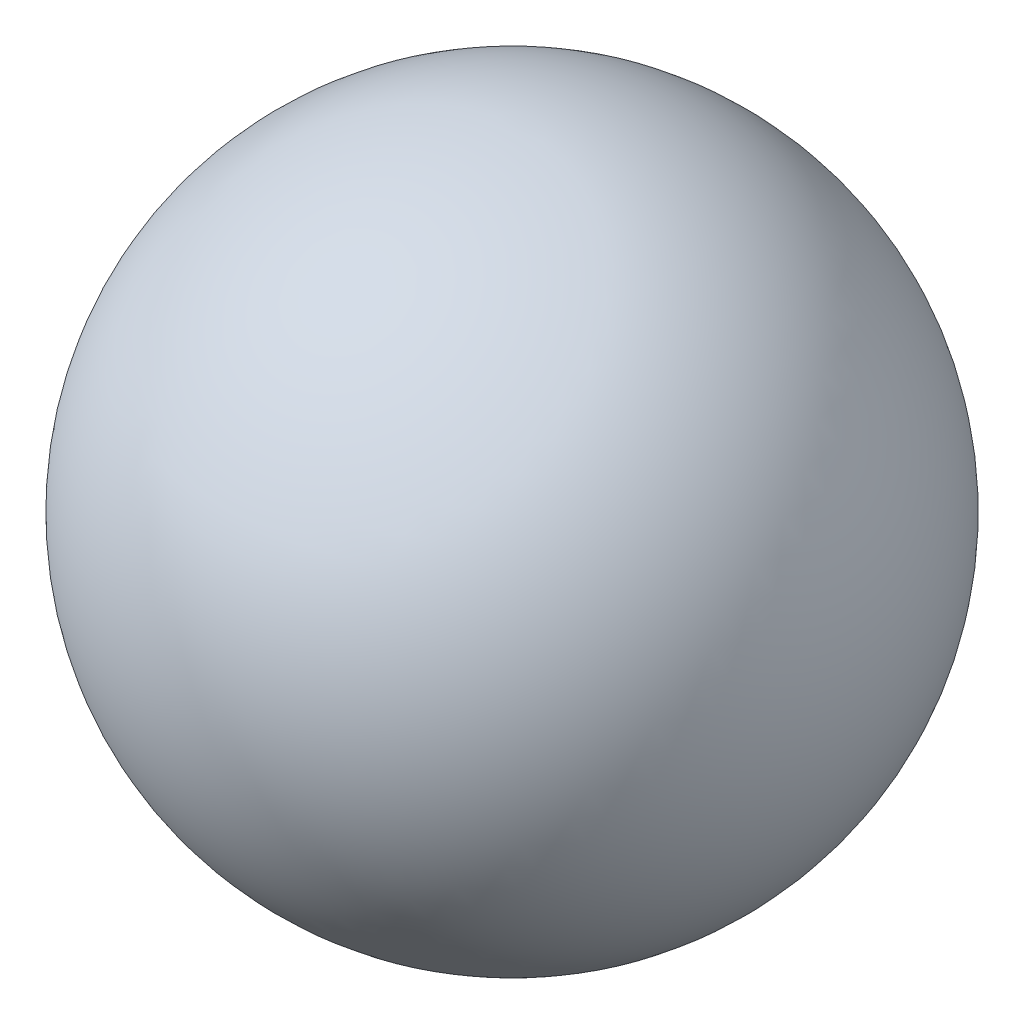
SolidWorks part; units mm, degrees
ref_plane "Front Plane" through (0, 0, 0) normal (0, 0, 1) x (1, 0, 0)
ref_plane "Top Plane" through (0, 0, 0) normal (0, 1, 0) x (1, 0, 0)
ref_plane "Right Plane" through (0, 0, 0) normal (1, 0, 0) x (0, 0, -1)
sketch "Sketch1" plane through (0, 0, 0) normal (0, 0, 1) x (1, 0, 0)
  line L0 (0, 25.4) -> (0, 22.86)
  line L1 (0, -22.86) -> (0, -25.4)
  arc A0 (0, 25.4) -> (0, -25.4) centre (0, 0) ccw
  arc A1 (0, 22.86) -> (0, -22.86) centre (0, 0) ccw
  dimension "D1" = 50.8
  dimension "D2" = 45.72
ref_axis "Axis1" through (0, 27.94, 0) along (0, -1, 0)
revolve "Revolve7" add sketch "Sketch1" angle 360 about L0
